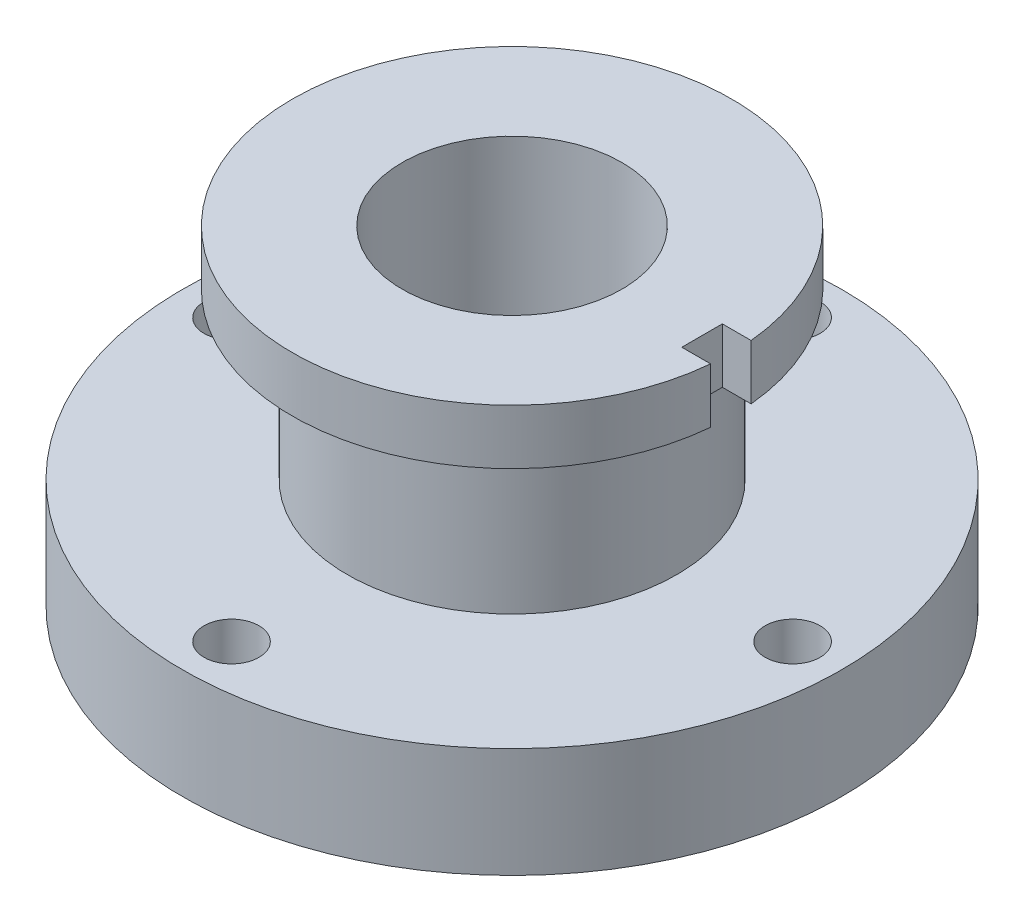
SolidWorks part; units mm, degrees
ref_plane "Front Plane" through (0, 0, 0) normal (0, 0, 1) x (1, 0, 0)
ref_plane "Top Plane" through (0, 0, 0) normal (0, 1, 0) x (1, 0, 0)
ref_plane "Right Plane" through (0, 0, 0) normal (1, 0, 0) x (0, 0, -1)
other "Center of Mass"
sketch "Sketch4" plane through (0, 0, 0) normal (0, 0, 1) x (1, 0, 0)
  line L0 (0, -251.6129) -> (0, -151.6129)
  line L1 (0, -251.6129) -> (300, -251.6129)
  line L2 (300, -251.6129) -> (300, -151.6129)
  line L3 (300, -151.6129) -> (150, -151.6129)
  line L4 (150, -151.6129) -> (150, -1.6129)
  line L5 (150, -1.6129) -> (200, -1.6129)
  line L6 (200, -1.6129) -> (200, 48.3871)
  line L7 (200, 48.3871) -> (152.8226, 48.3871)
  line L8 (152.8226, 48.3871) -> (100, 48.3871)
  line L9 (100, 48.3871) -> (100, -151.6129)
  line L10 (100, -151.6129) -> (0, -151.6129)
  line L11 (0, -251.6129) -> (0, 382.6571) construction
  dimension "D1" = 300
  dimension "D2" = 100
  dimension "D4" = 50
  dimension "D5" = 150
  dimension "D6" = 100
  dimension "D7" = 50
  dimension "D8" = 100
revolve "Revolve2" add sketch "Sketch4" angle 360 about L11
sketch "Sketch5" plane through (0, -151.6129, 0) normal (0, 1, 0) x (1, 0, 0)
  circle A0 centre (0, 255.3655) radius 25
  circle A2 centre (255.3655, 0) radius 25
  circle A3 centre (0, -255.3655) radius 25
  circle A4 centre (-255.3655, 0) radius 25
  dimension "D1" = 4
  dimension "D2" = 50
extrude "Cut-Extrude2" cut sketch "Sketch5" against normal blind 100
ref_axis "Base_Axis" through (0, -266.6129, 0) along (0, 1, 0)
sketch "Sketch6" plane through (0, 48.3871, 0) normal (0, 1, 0) x (1, 0, 0)
  line L1 (172.9439, 18.4456) -> (227.0561, 18.4456)
  line L2 (172.9439, 18.4456) -> (172.9439, -18.4456)
  line L3 (172.9439, -18.4456) -> (227.0561, -18.4456)
  line L4 (227.0561, 18.4456) -> (227.0561, -18.4456)
  line L5 (172.9439, 18.4456) -> (227.0561, -18.4456) construction
  line L6 (172.9439, -18.4456) -> (227.0561, 18.4456) construction
  circle A0 centre (0, 0) radius 200 construction
  point P2 (200, 0)
extrude "Cut-Extrude3" cut sketch "Sketch6" against normal blind 75
